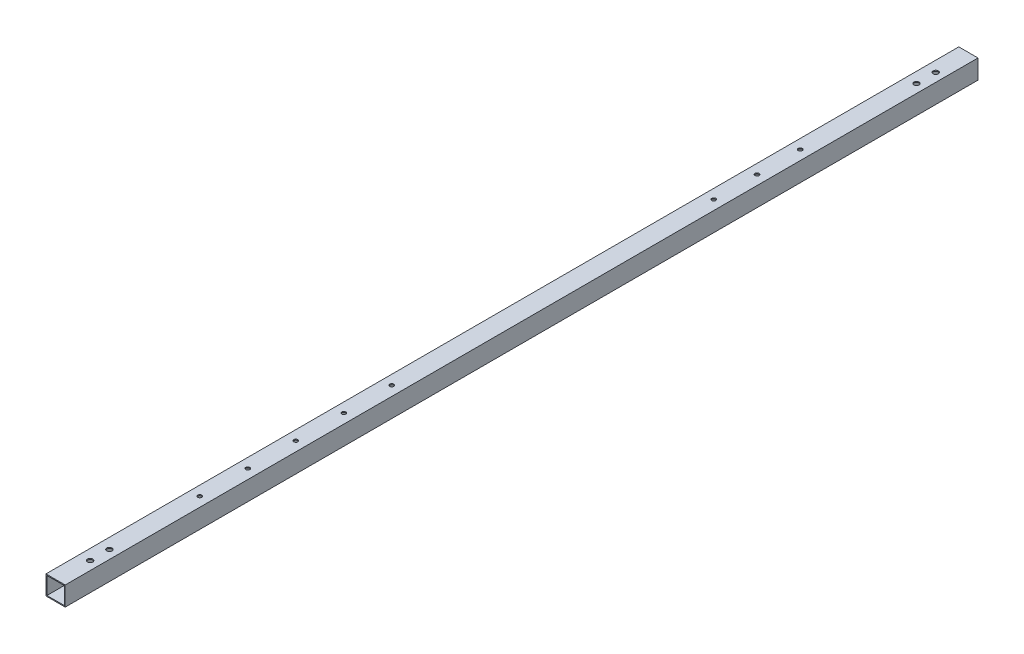
SolidWorks part; units mm, degrees
material "6061 合金"
ref_plane "前视基准面" through (0, 0, 0) normal (0, 0, 1) x (1, 0, 0)
ref_plane "上视基准面" through (0, 0, 0) normal (0, 1, 0) x (1, 0, 0)
ref_plane "右视基准面" through (0, 0, 0) normal (1, 0, 0) x (0, 0, -1)
other "Configuration Table"
sketch "草图1" plane through (0, 0, 0) normal (0, 0, 1) x (1, 0, 0)
  line L1 (0, 0) -> (20, 0)
  line L2 (0, 0) -> (0, -20)
  line L3 (0, -20) -> (20, -20)
  line L4 (20, 0) -> (20, -20)
  dimension "D1" = 20
extrude "拉伸-薄壁1" add sketch "草图1" along normal blind 950 thin thin type one direction reverse wall 1
sketch "草图2" plane through (0, 0, 0) normal (0, 1, 0) x (1, 0, 0)
  line L0 (20, -950) -> (20, 0) construction
  line L1 (20, 0) -> (0, 0) construction
  line L2 (20, -475) -> (-658.8172, -475) construction
  circle A0 centre (11, -35) radius 2.75
  circle A1 centre (11, -55) radius 2.75
  circle A2 centre (11, -895) radius 2.75
  circle A3 centre (11, -915) radius 2.75
  dimension "D1" = 5.5
  dimension "D2" = 9
  dimension "D3" = 35
  dimension "D5" = 20
  dimension "D4" = 2
extrude "切除-拉伸1" cut sketch "草图2" against normal blind 37
sketch "草图3" plane through (0, 0, 0) normal (0, 1, 0) x (1, 0, 0)
  line L0 (20, -950) -> (20, 0) construction
  circle A0 centre (10, -175) radius 2.1
  circle A1 centre (11, -55) radius 2.75 construction
  circle A2 centre (10, -220) radius 2.1
  circle A3 centre (10, -265) radius 2.1
  dimension "D1" = 4.2
  dimension "D2" = 120
  dimension "D3" = 10
  dimension "D5" = 45
  dimension "D4" = 3
extrude "切除-拉伸2" cut sketch "草图3" against normal blind 37
sketch "草图4" plane through (0, 0, 0) normal (0, 1, 0) x (1, 0, 0)
  line L0 (10, -950) -> (10, -522.0411) construction
  line L1 (20, -950) -> (0, -950) construction
  line L6 (10, -750) -> (10, -322.0411) construction
  line L7 (10, -800) -> (10, -372.0411) construction
  line L8 (10, -850) -> (10, -422.0411) construction
  line L9 (10, -900) -> (10, -472.0411) construction
  circle A0 centre (10, -800) radius 2.1
  circle A1 centre (10, -750) radius 2.1
  circle A2 centre (10, -700) radius 2.1
  circle A3 centre (10, -650) radius 2.1
  circle A4 centre (10, -600) radius 2.1
  dimension "D1" = 4.2
  dimension "D2" = 150
  dimension "D4" = 50
  dimension "D3" = 5
extrude "切除-拉伸3" cut sketch "草图4" against normal blind 37
